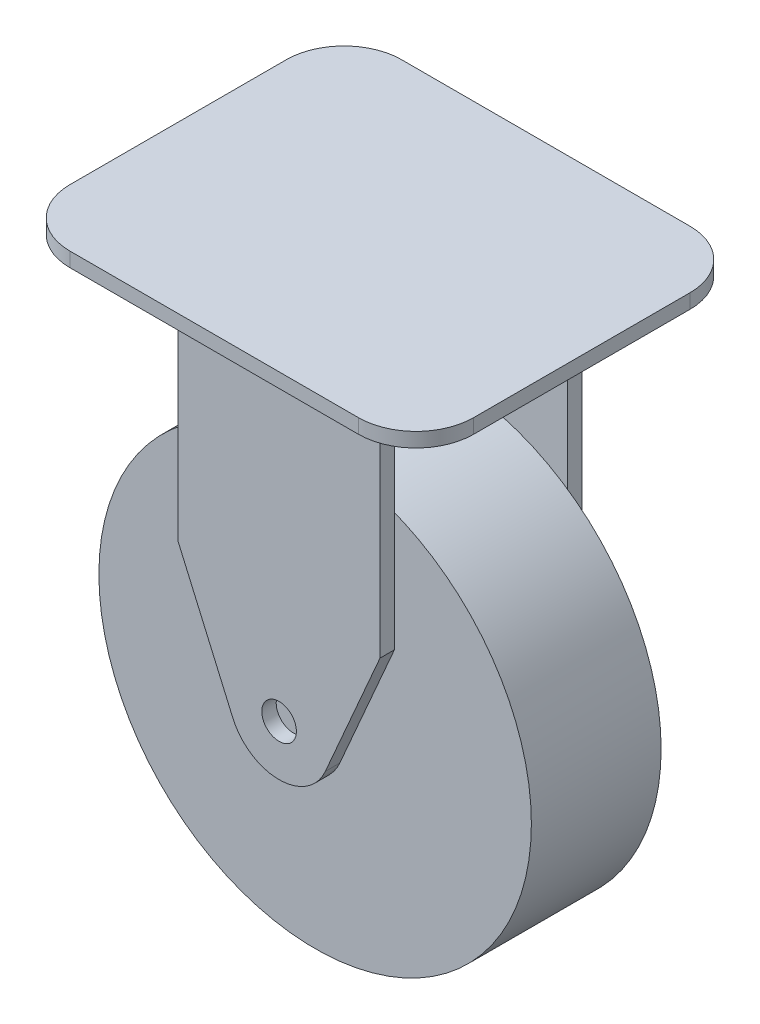
SolidWorks part; units mm, degrees
material "Ст 3 ГОСТ 380-88"
ref_plane "Спереди" through (0, 0, 0) normal (0, 0, 1) x (1, 0, 0)
ref_plane "Сверху" through (0, 0, 0) normal (0, 1, 0) x (1, 0, 0)
ref_plane "Справа" through (0, 0, 0) normal (1, 0, 0) x (0, 0, -1)
sketch "Sketch1" plane through (0, 0, 0) normal (0, 1, 0) x (1, 0, 0)
  line L1 (-50, 57.5) -> (50, 57.5)
  line L2 (-70, 37.5) -> (-70, -37.5)
  line L3 (-50, -57.5) -> (50, -57.5)
  line L4 (70, 37.5) -> (70, -37.5)
  line L5 (-70, 57.5) -> (70, -57.5) construction
  line L6 (-70, -57.5) -> (70, 57.5) construction
  arc A0 (-70, -37.5) -> (-50, -57.5) centre (-50, -37.5) ccw
  arc A1 (50, -57.5) -> (70, -37.5) centre (50, -37.5) ccw
  arc A2 (50, 57.5) -> (70, 37.5) centre (50, 37.5) cw
  arc A3 (-50, 57.5) -> (-70, 37.5) centre (-50, 37.5) ccw
  point P0 (0, 0)
  dimension "D3" = 20
  dimension "D1" = 140
  dimension "D2" = 115
extrude "Boss-Extrude1" add sketch "Sketch1" against normal blind 5
sketch "Sketch2" plane through (0, -5, 0) normal (0, -1, 0) x (1, 0, 0)
  line L12 (-55, 37.5) -> (-55, -37.5)
  line L13 (-50, -42.5) -> (50, -42.5)
  line L14 (55, -37.5) -> (55, 37.5)
  line L15 (50, 42.5) -> (-50, 42.5)
  line L16 (-55, 32.5) -> (-55, -32.5)
  line L17 (-45, -42.5) -> (45, -42.5)
  line L18 (55, -32.5) -> (55, 32.5)
  line L19 (45, 42.5) -> (-45, 42.5)
  arc A8 (-55, -32.5) -> (-45, -42.5) centre (-45, -32.5) ccw
  arc A9 (45, -42.5) -> (55, -32.5) centre (45, -32.5) ccw
  arc A10 (55, 32.5) -> (45, 42.5) centre (45, 32.5) ccw
  arc A11 (-55, 32.5) -> (-45, 42.5) centre (-45, 32.5) cw
  arc A16 (-50, 42.5) -> (-55, 37.5) centre (-50, 37.5) ccw
  arc A18 (-55, -37.5) -> (-50, -42.5) centre (-50, -37.5) ccw
  arc A20 (50, -42.5) -> (55, -37.5) centre (50, -37.5) ccw
  arc A22 (55, 37.5) -> (50, 42.5) centre (50, 37.5) ccw
  dimension "D2" = 10
  dimension "D1" = 15
extrude "Boss-Extrude2" add sketch "Sketch2" along normal blind 11
fillet "Fillet1" radius 10 8 edges at (-52.0711, -5, -39.5711) (-55, -5, 0) (-52.0711, -5, 39.5711) (0, -5, 42.5) (52.0711, -5, 39.5711) (55, -5, 0) (52.0711, -5, -39.5711) (0, -5, -42.5)
fillet "Fillet2" radius 8 8 edges at (-52.0711, -16, 39.5711) (0, -16, 42.5) (52.0711, -16, 39.5711) (55, -16, 0) (52.0711, -16, -39.5711) (0, -16, -42.5) (-52.0711, -16, -39.5711) (-55, -16, 0)
sketch "Sketch3" plane through (0, -16, 0) normal (0, -1, 0) x (1, 0, 0)
  line L1 (-35, 35) -> (35, 35)
  line L2 (-35, 35) -> (-35, -35)
  line L3 (-35, -35) -> (35, -35)
  line L4 (35, 35) -> (35, -35)
  line L5 (-35, 35) -> (35, -35) construction
  line L6 (-35, -35) -> (35, 35) construction
  point P0 (0, 0)
  dimension "D1" = 70
  dimension "D2" = 70
extrude "Boss-Extrude3" add sketch "Sketch3" along normal blind 5
sketch "Sketch4" plane through (0, 0, -35) normal (0, 0, -1) x (-1, 0, 0)
  line L0 (-35, -21) -> (-35, -91)
  line L1 (-35, -91) -> (-16.0423, -134.4926)
  line L2 (0, 20.9586) -> (0, -93.2031) construction
  line L4 (-51.2824, -145) -> (65.4328, -145) construction
  line L5 (-50, -5) -> (50, -5) construction
  line L6 (35, -91) -> (16.0423, -134.4926)
  line L7 (35, -21) -> (-35, -21) construction
  line L8 (35, -21) -> (-35, -21)
  line L9 (35, -21) -> (35, -91)
  arc A0 (-16.0423, -134.4926) -> (16.0423, -134.4926) centre (0, -127.5) ccw
  circle A1 centre (0, -127.5) radius 6
  dimension "D1" = 35
  dimension "D4" = 12
  dimension "D2" = 140
  dimension "D3" = 70
extrude "Boss-Extrude4" add sketch "Sketch4" against normal blind 5
mirror "Mirror1" about plane through (0, 0, 0) normal (0, 0, 1) of "Boss-Extrude4"
sketch "Sketch5" plane through (0, 0, 0) normal (0, 0, 1) x (1, 0, 0)
  circle A0 centre (0, -127.0201) radius 75
  dimension "D1" = 150
extrude "Boss-Extrude5" add sketch "Sketch5" along normal mid plane 45 separate body
